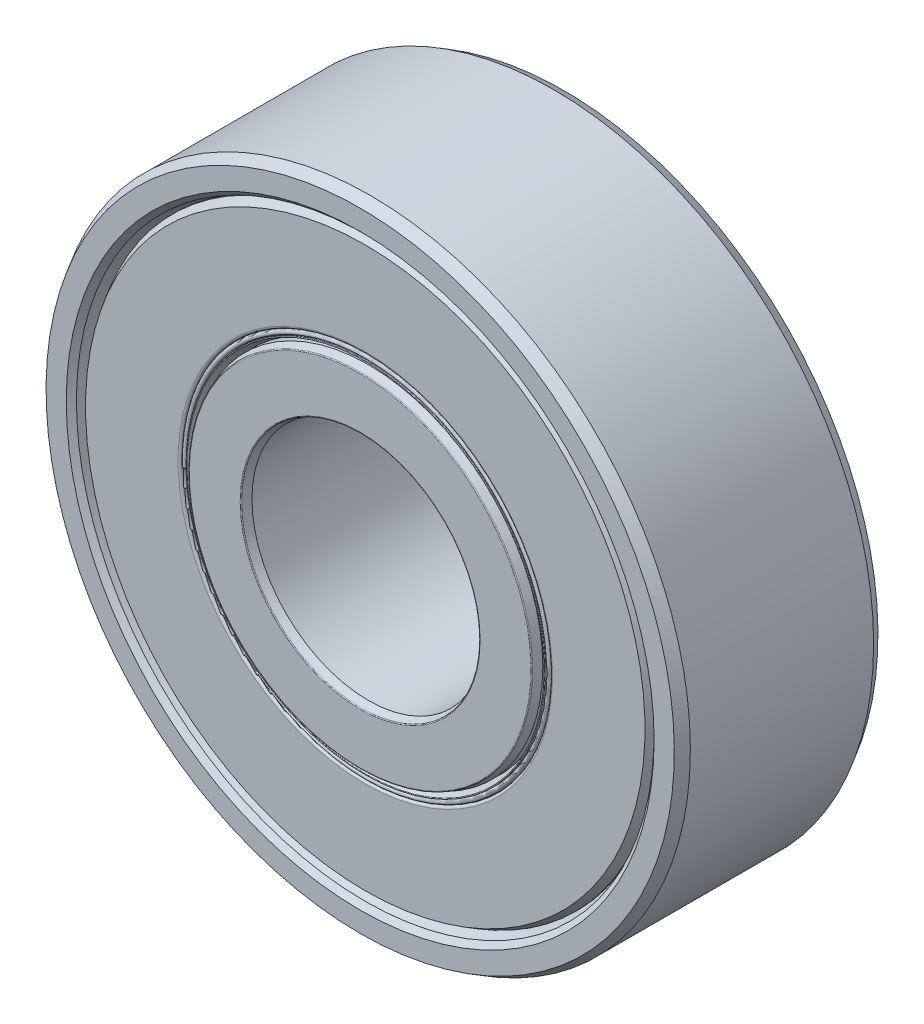
SolidWorks part; units mm, degrees
ref_plane "Front Plane" through (0, 0, 0) normal (0, 0, 1) x (1, 0, 0)
ref_plane "Top Plane" through (0, 0, 0) normal (0, 1, 0) x (1, 0, 0)
ref_plane "Right Plane" through (0, 0, 0) normal (1, 0, 0) x (0, 0, -1)
sketch "Sketch1" plane through (0, 0, 0) normal (0, 0, 1) x (1, 0, 0)
  line L0 (-11, 0) -> (11, 0) construction
  line L1 (-4, 0) -> (4, 0) construction
  circle A0 centre (0, 0) radius 4 construction
  circle A1 centre (0, 0) radius 11 construction
  point P3 (0, 0)
  point P6 (0, 0)
  point P7 (0, -4)
  point P11 (0, -11)
  point P12 (0, 4)
  point P13 (0, 11)
  dimension "OD" = 22
  dimension "ID" = 8
sketch "Sketch2" plane through (0, 0, 0) normal (1, 0, 0) x (0, 0, -1)
  line L0 (-3.5, 11) -> (3.5, 11) construction
  line L1 (0, 11) -> (0, -11) construction
  line L2 (3.15, 11) -> (-3.15, 11)
  line L3 (-3.15, 11) -> (-3.5, 10.7979)
  line L4 (-3.5, 10.7979) -> (-3.5, 10.1032)
  line L5 (-2.9452, 9.79) -> (-1.631, 9.79)
  line L6 (2.9452, 9.79) -> (1.631, 9.79)
  line L7 (3.5, 10.7979) -> (3.5, 10.1032)
  line L8 (3.15, 11) -> (3.5, 10.7979)
  line L9 (-1.631, 9.79) -> (-1.631, 11) construction
  line L10 (-1.631, 10.395) -> (0, 10.395) construction
  line L11 (0, 11) -> (0, -11) construction
  line L12 (-3.5, 0) -> (3.5, 0) construction
  line L13 (3.5, 4) -> (-3.5, 4) construction
  line L14 (-3.5, 4) -> (-3.5, -4) construction
  line L15 (-3.5, -4) -> (3.5, -4) construction
  line L16 (3.5, 11) -> (3.5, -11) construction
  line L20 (-2.9452, 9.79) -> (-3.325, 9.9282)
  line L21 (-3.325, 9.9282) -> (-3.5, 10.1032)
  line L26 (3.325, 9.9282) -> (3.5, 10.1032)
  line L27 (2.9452, 9.79) -> (3.325, 9.9282)
  arc A0 (-1.631, 9.79) -> (1.631, 9.79) centre (0, 7.894) cw
  circle A1 centre (0, 7.894) radius 2.501 construction
  point P17 (0, 0)
  point P21 (0, 11)
  point P30 (0, -4)
  dimension "Width" = 7
  dimension "D3" = 3.262
  dimension "For Shaft Diameter" = 8
  dimension "For Housing ID" = 22
  dimension "D4" = 19.58
  dimension "D2" = 20
  dimension "D5" = 45
  dimension "D1" = 30
  dimension "D6" = 0.35
  dimension "D7" = 0.175
sketch "Sketch3" plane through (0, 0, 0) normal (1, 0, 0) x (0, 0, -1)
  line L14 (-2.9452, 9.79) -> (-3.325, 9.9282) construction
  line L15 (-3.325, 9.9282) -> (-3.5, 10.1032) construction
  line L16 (-3.5, 10.7979) -> (-3.5, 10.1032) construction
  line L17 (-3.15, 11) -> (-3.5, 10.7979) construction
  line L18 (3.15, 11) -> (-3.15, 11) construction
  line L19 (3.15, 11) -> (3.5, 10.7979) construction
  line L20 (3.5, 10.7979) -> (3.5, 10.1032) construction
  line L21 (3.325, 9.9282) -> (3.5, 10.1032) construction
  line L22 (2.9452, 9.79) -> (3.325, 9.9282) construction
  line L23 (2.9452, 9.79) -> (1.631, 9.79) construction
  line L24 (-2.9452, 9.79) -> (-1.631, 9.79) construction
  line L25 (-2.9452, 9.79) -> (-3.325, 9.9282)
  line L26 (-3.325, 9.9282) -> (-3.5, 10.1032)
  line L27 (-3.5, 10.7979) -> (-3.5, 10.1032)
  line L28 (-3.15, 11) -> (-3.5, 10.7979)
  line L29 (3.15, 11) -> (-3.15, 11)
  line L30 (3.15, 11) -> (3.5, 10.7979)
  line L31 (3.5, 10.7979) -> (3.5, 10.1032)
  line L32 (3.325, 9.9282) -> (3.5, 10.1032)
  line L33 (2.9452, 9.79) -> (3.325, 9.9282)
  line L34 (2.9452, 9.79) -> (1.631, 9.79)
  line L35 (-2.9452, 9.79) -> (-1.631, 9.79)
  arc A2 (1.631, 9.79) -> (-1.631, 9.79) centre (0, 7.894) ccw construction
  arc A3 (1.631, 9.79) -> (-1.631, 9.79) centre (0, 7.894) ccw
revolve "Revolve1" add sketch "Sketch3" angle 360 about L12
sketch "Sketch4" plane through (0, 0, 0) normal (1, 0, 0) x (0, 0, -1)
  line L0 (0, 11) -> (0, -11) construction
  line L1 (0, 11) -> (0, -11) construction
  line L2 (-3.22, 4) -> (-3.477, 4.0935)
  line L3 (-3.5, 4.1264) -> (-3.5, 5.8716)
  line L4 (3.22, 5.998) -> (3.477, 5.9045)
  line L5 (-3.22, 5.998) -> (-1.631, 5.998)
  line L6 (-3.22, 4) -> (3.22, 4)
  line L7 (3.5, 10.7979) -> (3.5, 10.1032) construction
  line L8 (3.22, 4) -> (3.477, 4.0935)
  line L9 (1.631, 5.998) -> (1.631, 4) construction
  line L10 (3.5, 4.1264) -> (3.5, 5.8716)
  line L11 (3.22, 5.998) -> (1.631, 5.998)
  line L12 (-3.22, 5.998) -> (-3.477, 5.9045)
  line L14 (1.631, 4.999) -> (3.5, 4.999) construction
  circle A0 centre (0, 7.894) radius 2.501 construction
  arc A1 (1.631, 5.998) -> (-1.631, 5.998) centre (0, 7.894) cw
  arc A2 (3.477, 5.9045) -> (3.5, 5.8716) centre (3.465, 5.8716) cw
  arc A3 (-3.477, 5.9045) -> (-3.5, 5.8716) centre (-3.465, 5.8716) ccw
  arc A4 (3.477, 4.0935) -> (3.5, 4.1264) centre (3.465, 4.1264) ccw
  arc A5 (-3.477, 4.0935) -> (-3.5, 4.1264) centre (-3.465, 4.1264) cw
  point P14 (3.5, 4.1019)
  dimension "D2" = 0.035
  dimension "D1" = 20
  dimension "D3" = 0.28
revolve "Revolve2" add sketch "Sketch4" angle 360 about L12
sketch "Sketch5" plane through (0, 0, 0) normal (1, 0, 0) x (0, 0, -1)
  line L0 (-2.501, 7.894) -> (2.501, 7.894)
  arc A2 (-2.501, 7.894) -> (2.501, 7.894) centre (0, 7.894) cw
  arc A3 (1.631, 9.79) -> (-1.631, 9.79) centre (0, 7.894) ccw construction
revolve "Revolve3" add sketch "Sketch5" angle 360 about L0
pattern_circular "CirPattern1" count 7 over 360 about axis through (0, 0, 3.5) along (0, 0, -1) of bodies 104
sketch "Sketch6" plane through (0, 0, 0) normal (1, 0, 0) x (0, 0, -1)
  line L1 (-3.0219, 9.79) -> (-2.501, 9.79)
  line L2 (-3.325, 9.615) -> (-3.325, 6.4355)
  line L3 (-3.2375, 6.348) -> (-2.501, 6.348)
  line L4 (-2.501, 9.79) -> (-2.501, 6.348)
  line L6 (-3.15, 11) -> (-3.5, 10.7979) construction
  line L7 (0, 11) -> (0, 4) construction
  line L8 (3.2375, 6.348) -> (2.501, 6.348)
  line L9 (2.501, 9.79) -> (2.501, 6.348)
  line L10 (3.0219, 9.79) -> (2.501, 9.79)
  line L11 (3.325, 9.615) -> (3.325, 6.4355)
  line L13 (-3.22, 5.998) -> (-1.631, 5.998) construction
  line L14 (-3.325, 9.615) -> (-3.0219, 9.79)
  line L15 (-2.9452, 9.79) -> (-1.631, 9.79) construction
  line L16 (3.325, 9.615) -> (3.0219, 9.79)
  arc A0 (-3.325, 6.4355) -> (-3.2375, 6.348) centre (-3.2375, 6.4355) ccw
  circle A1 centre (0, 7.894) radius 2.501 construction
  arc A2 (3.325, 6.4355) -> (3.2375, 6.348) centre (3.2375, 6.4355) cw
  point P10 (-3.325, 10.899)
  point P26 (-3.325, 6.348)
  dimension "D3" = 0.0875
  dimension "D1" = 0.35
  dimension "D2" = 0.175
revolve "Revolve4" add sketch "Sketch6" angle 360 about L12
sketch "Sketch7" plane through (0, 0, 0) normal (1, 0, 0) x (0, 0, -1)
  line L0 (-2.501, 5.998) -> (-2.9259, 5.998)
  line L5 (-2.9259, 5.998) -> (-3.3135, 6.1391)
  line L6 (-3.3075, 6.173) -> (-3.2375, 6.173)
  line L7 (0, 5.393) -> (0, 4) construction
  line L8 (0, 11) -> (0, -11) construction
  line L9 (-3.2375, 6.348) -> (-2.501, 6.348)
  line L12 (-2.501, 6.348) -> (-2.501, 5.998)
  line L13 (-3.22, 5.998) -> (-1.631, 5.998) construction
  line L14 (-3.2375, 6.348) -> (-2.501, 6.348) construction
  line L15 (-2.501, 9.79) -> (-2.501, 6.348) construction
  line L16 (2.501, 6.348) -> (2.501, 5.998)
  line L17 (3.2375, 6.348) -> (2.501, 6.348)
  line L18 (3.3075, 6.173) -> (3.2375, 6.173)
  line L19 (2.9259, 5.998) -> (3.3135, 6.1391)
  line L20 (2.501, 5.998) -> (2.9259, 5.998)
  circle A2 centre (0, 7.894) radius 2.501 construction
  arc A5 (-3.3135, 6.1391) -> (-3.3075, 6.173) centre (-3.3075, 6.1555) cw
  arc A6 (-3.2375, 6.173) -> (-3.2375, 6.348) centre (-3.2375, 6.2605) cw
  arc A7 (3.2375, 6.173) -> (3.2375, 6.348) centre (3.2375, 6.2605) ccw
  arc A8 (3.3135, 6.1391) -> (3.3075, 6.173) centre (3.3075, 6.1555) ccw
  point P14 (-3.325, 6.2605)
  point P27 (-2.501, 6.173)
  point P36 (-3.325, 6.1555)
  dimension "D1" = 20
  dimension "D2" = 0.0175
revolve "Revolve5" add sketch "Sketch7" angle 360 about L12
equation "\"D3@Sketch2\"=\"Width@Sketch2\" *.466"
equation "\"D4@Sketch2\"=\"OD@Sketch1\"*.89"
equation "\"D1@Sketch6\"=(\"OD@Sketch1\"-\"ID@Sketch1\")*.025"
equation "\"D2@Sketch6\"=\"D1@Sketch6\"*.5"
equation "\"D3@Sketch6\"=\"D1@Sketch6\"*.25"
equation "\"D3@Sketch4\"=\"Width@Sketch2\"*.04"
equation "\"D2@Sketch4\"=\"D3@Sketch4\"*.125"
equation "\"D6@Sketch2\"=\"Width@Sketch2\"*.05"
equation "\"D7@Sketch2\"=\"D6@Sketch2\"*.5"
equation "\"D2@Sketch7\"=\"D6@Sketch2\"*.05"
